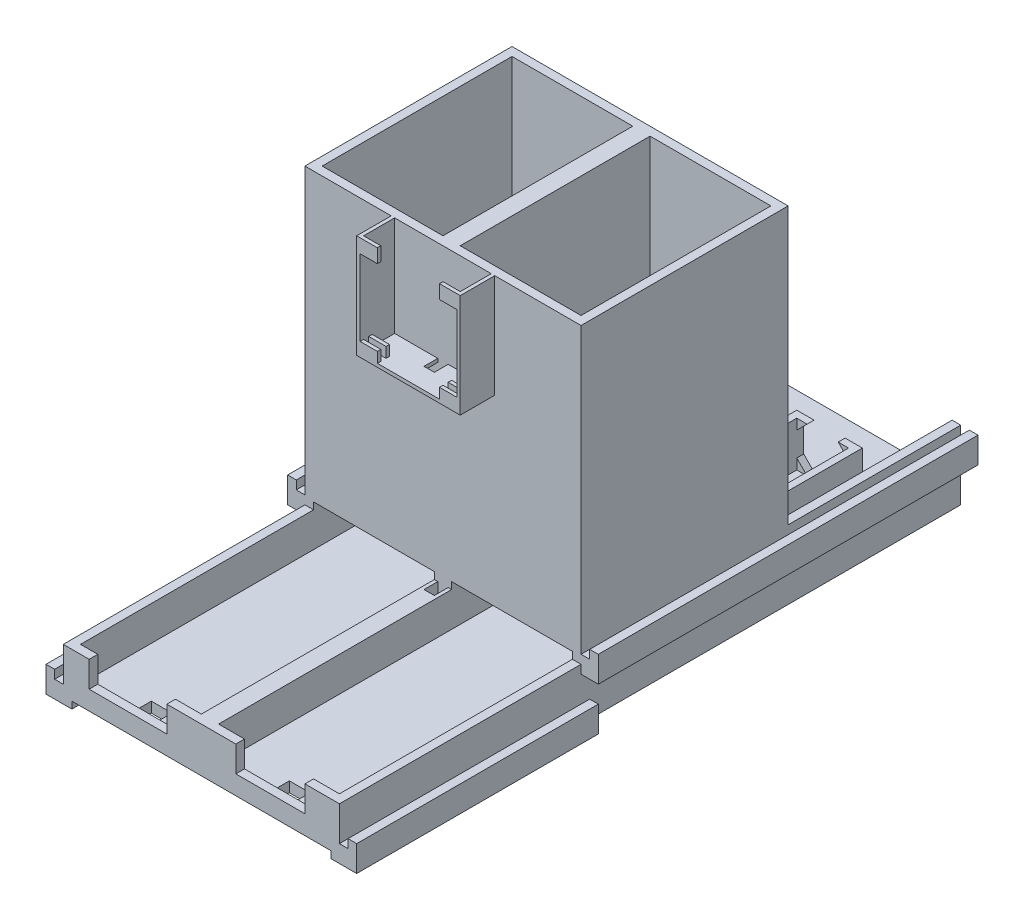
SolidWorks part; units mm, degrees
ref_plane "Front Plane" through (0, 0, 0) normal (0, 0, 1) x (1, 0, 0)
ref_plane "Top Plane" through (0, 0, 0) normal (0, 1, 0) x (1, 0, 0)
ref_plane "Right Plane" through (0, 0, 0) normal (1, 0, 0) x (0, 0, -1)
sketch "Sketch1" plane through (0, 0, 0) normal (0, 1, 0) x (1, 0, 0)
  line L1 (0, 0) -> (80, 0)
  line L2 (0, 0) -> (0, 60)
  line L3 (0, 60) -> (80, 60)
  line L4 (80, 0) -> (80, 60)
sketch "Sketch2" plane through (0, 0, 0) normal (0, 1, 0) x (1, 0, 0)
  line L1 (2.5, 57.5) -> (37.5, 57.5)
  line L2 (2.5, 57.5) -> (2.5, 2.5)
  line L3 (2.5, 2.5) -> (37.5, 2.5)
  line L4 (37.5, 57.5) -> (37.5, 2.5)
  line L5 (42.5, 57.5) -> (77.5, 57.5)
  line L6 (42.5, 57.5) -> (42.5, 2.5)
  line L7 (42.5, 2.5) -> (77.5, 2.5)
  line L8 (77.5, 57.5) -> (77.5, 2.5)
extrude "Boss-Extrude1" add sketch "Sketch1" along normal blind 100
extrude "Cut-Extrude1" cut sketch "Sketch2" along normal blind 95 from offset 5
sketch "Sketch3" plane through (0, 0, 0) normal (0, 0, 1) x (1, 0, 0)
  line L0 (80, 100) -> (80, 0) construction
  line L1 (0, 0) -> (80, 0)
  line L2 (0, 0) -> (0, 5)
  line L3 (0, 5) -> (80, 5)
  line L4 (80, 0) -> (80, 5)
extrude "Boss-Extrude2" add sketch "Sketch3" along normal blind 70
sketch "Sketch4" plane through (0, 5, 0) normal (0, 1, 0) x (1, 0, 0)
  line L0 (80, 0) -> (77.5, 0)
  line L5 (0, 0) -> (0, -70)
  line L18 (0, -70) -> (80, -70)
  line L19 (80, -70) -> (80, 0)
  line L20 (80, 0) -> (0, 0) construction
  line L21 (77.5, 0) -> (77.5, -67.5)
  line L22 (77.5, -67.5) -> (42.5, -67.5)
  line L23 (42.5, -67.5) -> (42.5, 0)
  line L24 (0, 0) -> (80, 0) construction
  line L25 (42.5, 0) -> (37.5, 0)
  line L26 (37.5, 0) -> (37.5, -67.5)
  line L27 (37.5, -67.5) -> (2.5, -67.5)
  line L28 (2.5, -67.5) -> (2.5, 0)
  line L29 (2.5, 0) -> (0, 0)
extrude "Boss-Extrude3" add sketch "Sketch4" along normal blind 10
sketch "Sketch5" plane through (0, 15, 0) normal (0, 1, 0) x (1, 0, 0)
  line L0 (37.5, -67.5) -> (2.5, -67.5) construction
  line L1 (7.5, -67.5) -> (30, -67.5)
  line L2 (7.5, -67.5) -> (7.5, -70)
  line L3 (7.5, -70) -> (30, -70)
  line L4 (30, -67.5) -> (30, -70)
  line L5 (0, -70) -> (80, -70) construction
  line L6 (77.5, -67.5) -> (42.5, -67.5) construction
  line L7 (70, -67.5) -> (50, -67.5)
  line L8 (70, -67.5) -> (70, -70)
  line L9 (70, -70) -> (50, -70)
  line L10 (50, -67.5) -> (50, -70)
  line L11 (0, 0) -> (0, -70) construction
  line L12 (37.5, 0) -> (37.5, -67.5) construction
  line L13 (42.5, -67.5) -> (42.5, 0) construction
  line L14 (77.5, 0) -> (77.5, -67.5) construction
  dimension "D1" = 7.5
  dimension "D2" = 7.5
  dimension "D3" = 7.5
  dimension "D4" = 7.5
extrude "Cut-Extrude2" cut sketch "Sketch5" against normal blind 7.5
sketch "Sketch6" plane through (0, 0, 0) normal (0, 0, 1) x (1, 0, 0)
  line L1 (2.5, 17) -> (37.5, 17)
  line L2 (2.5, 17) -> (2.5, 5)
  line L3 (2.5, 5) -> (37.5, 5)
  line L4 (37.5, 17) -> (37.5, 5)
  line L5 (42.5, 5) -> (77.5, 5)
  line L6 (42.5, 5) -> (42.5, 17)
  line L7 (42.5, 17) -> (77.5, 17)
  line L8 (77.5, 5) -> (77.5, 17)
extrude "Cut-Extrude4" cut sketch "Sketch6" against normal blind 57.5
sketch "Sketch7" plane through (0, 0, -60) normal (0, 0, -1) x (-1, 0, 0)
  circle A0 centre (-20, 11.5) radius 4
  circle A1 centre (-60, 11.5) radius 4
extrude "Cut-Extrude6" cut sketch "Sketch7" against normal up to next
sketch "Sketch9" plane through (0, 0, 0) normal (0, 1, 0) x (1, 0, 0)
  line L1 (0, 60) -> (80, 60)
  line L2 (0, 60) -> (0, 110)
  line L3 (0, 110) -> (80, 110)
  line L4 (80, 60) -> (80, 110)
extrude "Boss-Extrude4" add sketch "Sketch9" along normal blind 5
sketch "Sketch11" plane through (0, 0, 0) normal (0, -1, 0) x (1, 0, 0)
  line L1 (2.5, 70) -> (77.5, 70)
  line L2 (2.5, 70) -> (2.5, 37.5)
  line L3 (2.5, 37.5) -> (77.5, 37.5)
  line L4 (77.5, 70) -> (77.5, 37.5)
  line L6 (0, 70) -> (80, 70) construction
extrude "Cut-Extrude7" cut sketch "Sketch11" against normal blind 2
sketch "Sketch13" plane through (0, 5, 0) normal (0, 1, 0) x (1, 0, 0)
  line L0 (37.5, -67.5) -> (2.5, -67.5) construction
  line L1 (17, -67.5) -> (23, -67.5)
  line L2 (17, -67.5) -> (17, -61.5)
  line L3 (17, -61.5) -> (23, -61.5)
  line L4 (23, -67.5) -> (23, -61.5)
  line L5 (77.5, -67.5) -> (42.5, -67.5) construction
  line L6 (57, -67.5) -> (63, -67.5)
  line L7 (57, -67.5) -> (57, -61.5)
  line L8 (57, -61.5) -> (63, -61.5)
  line L9 (63, -67.5) -> (63, -61.5)
extrude "Cut-Extrude8" cut sketch "Sketch13" against normal through all
sketch "Sketch14" plane through (0, 0, 0) normal (0, 0, 1) x (1, 0, 0)
  line L0 (0, 100) -> (80, 100) construction
  line L1 (25, 100) -> (26, 100)
  line L2 (25, 100) -> (25, 70)
  line L3 (25, 70) -> (26, 70)
  line L4 (26, 100) -> (26, 71)
  line L6 (54, 100) -> (55, 100)
  line L7 (54, 100) -> (54, 71)
  line L8 (54, 70) -> (55, 70)
  line L9 (55, 100) -> (55, 70)
  line L10 (26, 70) -> (54, 70)
  line L12 (26, 71) -> (54, 71)
  dimension "D1" = 30
  dimension "D2" = 1
  dimension "D3" = 1
extrude "Boss-Extrude5" add sketch "Sketch14" along normal blind 10
sketch "Sketch15" plane through (0, 0, 10) normal (0, 0, 1) x (1, 0, 0)
  line L0 (26, 71) -> (26, 100) construction
  line L1 (25, 70) -> (31, 70)
  line L2 (25, 70) -> (25, 74)
  line L3 (25, 74) -> (31, 74)
  line L4 (31, 70) -> (31, 74)
  line L5 (54, 71) -> (26, 71) construction
  line L6 (40, 70) -> (40, 81.9127) construction
  line L7 (25, 70) -> (55, 70) construction
  line L8 (26, 71) -> (26, 100) construction
  line L10 (49, 70) -> (49, 74)
  line L11 (55, 74) -> (49, 74)
  line L12 (55, 70) -> (55, 74)
  line L13 (55, 70) -> (49, 70)
  dimension "D1" = 5
  dimension "D2" = 3
  dimension "D3" = 14
sketch "Sketch17" plane through (0, 0, 10) normal (0, 0, 1) x (1, 0, 0)
  line L1 (25, 100) -> (31, 100)
  line L2 (25, 100) -> (25, 96)
  line L3 (25, 96) -> (31, 96)
  line L4 (31, 100) -> (31, 96)
  line L5 (55, 100) -> (49, 100)
  line L6 (55, 100) -> (55, 96)
  line L7 (55, 96) -> (49, 96)
  line L8 (49, 100) -> (49, 96)
  dimension "D1" = 6
  dimension "D2" = 4
  dimension "D3" = 6
  dimension "D4" = 4
extrude "Boss-Extrude6" add sketch "Sketch15" against normal blind 1
extrude "Boss-Extrude7" add sketch "Sketch15<2>" against normal blind 1 from offset 2.5 offset against normal yes
sketch "Sketch15<2>" plane through (0, 0, 10) normal (0, 0, 1) x (1, 0, 0) same geometry as "Sketch15"
extrude "Boss-Extrude8" add sketch "Sketch17" against normal blind 1
sketch "Sketch18" plane through (0, 71, 0) normal (0, 1, 0) x (1, 0, 0)
  line L5 (42.5, 57.5) -> (42.5, -67.5) construction
  line L7 (54, 0) -> (26, 0) construction
  line L8 (38.5, 0) -> (41.5, 0)
  line L9 (38.5, 0) -> (38.5, -4)
  line L10 (38.5, -4) -> (41.5, -4)
  line L11 (41.5, 0) -> (41.5, -4)
  line L12 (37.5, -67.5) -> (37.5, 57.5) construction
  dimension "D1" = 1
  dimension "D2" = 1
  dimension "D3" = 4
extrude "Cut-Extrude9 (OLED Cable)" cut sketch "Sketch18" against normal through all
sketch "Sketch20" plane through (0, 5, 0) normal (0, 1, 0) x (1, 0, 0)
  line L0 (0, 60) -> (80, 60) construction
  line L1 (62.5, 60) -> (57.5, 60)
  line L2 (62.5, 60) -> (62.5, 65)
  line L3 (62.5, 65) -> (57.5, 65)
  line L4 (57.5, 60) -> (57.5, 65)
  line L5 (80, 60) -> (80, 110) construction
  line L7 (40, 110) -> (40, 60) construction
  line L8 (80, 110) -> (0, 110) construction
  line L9 (17.5, 65) -> (22.5, 65)
  line L10 (22.5, 60) -> (22.5, 65)
  line L11 (17.5, 60) -> (22.5, 60)
  line L12 (17.5, 60) -> (17.5, 65)
  point P8 (60, 60)
  dimension "D1" = 5
  dimension "D2" = 17.5
  dimension "D3" = 5
  dimension "D4" = 40
extrude "Cut-Extrude10 (Solenoid Wire)" cut sketch "Sketch20" against normal through all
sketch "Sketch21" plane through (0, 5, 0) normal (0, 1, 0) x (1, 0, 0)
  line L0 (62.5, 60) -> (80, 60) construction
  line L1 (67.5, 60) -> (69.5, 60)
  line L2 (67.5, 60) -> (67.5, 92)
  line L3 (67.5, 92) -> (69.5, 92)
  line L4 (69.5, 60) -> (69.5, 92)
  line L7 (80, 110) -> (0, 110) construction
  line L9 (40, 60) -> (40, 110) construction
  line L10 (22.5, 60) -> (57.5, 60) construction
  line L11 (0, 110) -> (0, 60) construction
  line L12 (60, 110) -> (60, 60) construction
  line L13 (80, 60) -> (80, 110) construction
  line L15 (50.5, 60) -> (50.5, 92)
  line L16 (52.5, 92) -> (50.5, 92)
  line L17 (52.5, 60) -> (52.5, 92)
  line L18 (52.5, 60) -> (50.5, 60)
  line L19 (27.5, 60) -> (29.5, 60)
  line L20 (27.5, 60) -> (27.5, 92)
  line L21 (29.5, 60) -> (29.5, 92)
  line L22 (27.5, 92) -> (29.5, 92)
  line L23 (10.5, 60) -> (10.5, 92)
  line L24 (12.5, 92) -> (10.5, 92)
  line L25 (12.5, 60) -> (12.5, 92)
  line L26 (12.5, 60) -> (10.5, 60)
  dimension "D1" = 2
  dimension "D2" = 40
  dimension "D3" = 20
  dimension "D4" = 7.5
  dimension "D5" = 32
extrude "Boss-Extrude9 (Solenoid Side Support)" add sketch "Sketch21" along normal blind 13
sketch "Sketch25" plane through (0, 0, -92) normal (0, 0, -1) x (-1, 0, 0)
  line L0 (-60, 0) -> (-60, 21.3678) construction
  line L1 (-62.5, 5) -> (-67.5, 5) construction
  line L2 (-80, 0) -> (0, 0) construction
  line L3 (-67.5, 18) -> (-67.5, 5) construction
  line L4 (-40, 0) -> (-40, 19.3366) construction
  line L5 (-69.5, 11.5) -> (-50.5, 11.5) construction
  line L6 (-55.5, 18) -> (-52.5, 18)
  line L7 (-69.5, 18) -> (-69.5, 5) construction
  line L8 (-50.5, 18) -> (-50.5, 5) construction
  line L9 (0, 100) -> (0, 5) construction
  line L10 (-52.5, 5) -> (-52.5, 8)
  line L11 (-52.5, 18) -> (-52.5, 5) construction
  line L12 (-52.5, 8) -> (-55.5, 5)
  line L13 (-52.5, 5) -> (-57.5, 5) construction
  line L14 (-55.5, 5) -> (-52.5, 5)
  line L15 (-52.5, 15) -> (-55.5, 18)
  line L16 (-52.5, 18) -> (-52.5, 15)
  line L17 (-67.5, 18) -> (-67.5, 15)
  line L18 (-67.5, 15) -> (-64.5, 18)
  line L19 (-64.5, 5) -> (-67.5, 5)
  line L20 (-67.5, 8) -> (-64.5, 5)
  line L21 (-67.5, 5) -> (-67.5, 8)
  line L22 (-64.5, 18) -> (-67.5, 18)
  line L23 (-15.5, 18) -> (-12.5, 18)
  line L24 (-12.5, 5) -> (-12.5, 8)
  line L25 (-12.5, 8) -> (-15.5, 5)
  line L26 (-15.5, 5) -> (-12.5, 5)
  line L27 (-12.5, 15) -> (-15.5, 18)
  line L28 (-12.5, 18) -> (-12.5, 15)
  line L29 (-27.5, 18) -> (-27.5, 15)
  line L30 (-27.5, 15) -> (-24.5, 18)
  line L31 (-24.5, 5) -> (-27.5, 5)
  line L32 (-27.5, 8) -> (-24.5, 5)
  line L33 (-27.5, 5) -> (-27.5, 8)
  line L34 (-24.5, 18) -> (-27.5, 18)
  dimension "D1" = 6.5
  dimension "D2" = 7.5
  dimension "D3" = 40
  dimension "D4" = 3
  dimension "D5" = 3
extrude "Boss-Extrude12 (Solenoid Rear Support)" add sketch "Sketch25" against normal blind 2
sketch "Sketch27" plane through (0, 5, 0) normal (0, 1, 0) x (1, 0, 0)
  line L0 (80, 110) -> (0, 110) construction
  line L1 (80, 60) -> (77.5, 60)
  line L2 (80, 60) -> (80, 110)
  line L3 (80, 110) -> (77.5, 110)
  line L4 (77.5, 60) -> (77.5, 110)
  line L6 (0, 60) -> (2.5, 60)
  line L7 (0, 60) -> (0, 110)
  line L8 (0, 110) -> (2.5, 110)
  line L9 (2.5, 60) -> (2.5, 110)
  dimension "D1" = 2.5
  dimension "D2" = 2.5
extrude "Boss-Extrude13 (Solenoid Section Walls)" add sketch "Sketch27" along normal blind 15
sketch "Sketch29" plane through (80, 0, 0) normal (1, 0, 0) x (0, 0, -1)
  line L0 (-70, 0) -> (-70, 15) construction
  line L1 (-70, 5) -> (0, 5)
  line L2 (-70, 5) -> (-70, 0)
  line L3 (-70, 0) -> (0, 0)
  line L4 (0, 5) -> (0, 0)
  line L6 (-70, 0) -> (110, 0) construction
  line L7 (110, 20) -> (110, 0) construction
  line L8 (110, 17.5) -> (0, 17.5)
  line L9 (110, 17.5) -> (110, 12.5)
  line L10 (110, 12.5) -> (0, 12.5)
  line L11 (0, 17.5) -> (0, 12.5)
  line L12 (60, 20) -> (110, 20) construction
  dimension "D1" = 5
  dimension "D2" = 5
  dimension "D3" = 2.5
extrude "Boss-Extrude14 (Guide)" add sketch "Sketch29" along normal blind 5
extrude "Boss-Extrude15" add sketch "Sketch29<2>" against normal blind 5 from offset 80 offset against normal yes
sketch "Sketch29<2>" plane through (80, 0, 0) normal (1, 0, 0) x (0, 0, -1) same geometry as "Sketch29"
sketch "Sketch30" plane through (85, 0, 0) normal (1, 0, 0) x (0, 0, -1)
  line L1 (0, 17.5) -> (110, 17.5)
  line L2 (0, 17.5) -> (0, 20)
  line L3 (0, 20) -> (110, 20)
  line L4 (110, 17.5) -> (110, 20)
  line L5 (-70, 5) -> (0, 5)
  line L6 (-70, 5) -> (-70, 7.5)
  line L7 (-70, 7.5) -> (0, 7.5)
  line L8 (0, 5) -> (0, 7.5)
  dimension "D1" = 2.5
extrude "Boss-Extrude16" add sketch "Sketch30" against normal blind 2.5
extrude "Boss-Extrude17" add sketch "Sketch30<2>" against normal blind 2.5 from offset 87.5 offset against normal yes
sketch "Sketch30<2>" plane through (85, 0, 0) normal (1, 0, 0) x (0, 0, -1) same geometry as "Sketch30"
